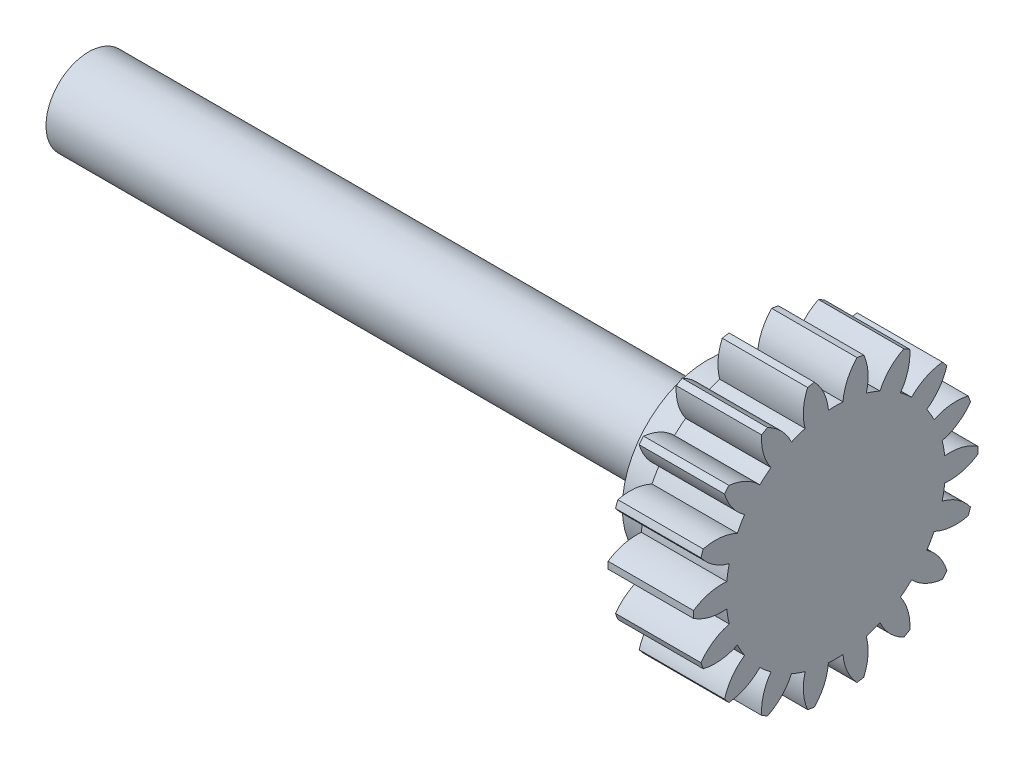
SolidWorks part; units mm, degrees
material "PET"
ref_plane "Plane1" through (0, 0, 0) normal (0, 0, 1) x (1, 0, 0)
ref_plane "Plane2" through (0, 0, 0) normal (0, 1, 0) x (1, 0, 0)
ref_plane "Plane3" through (0, 0, 0) normal (1, 0, 0) x (0, 0, -1)
sketch "HoldingSke" plane through (0, 0, 0) normal (0, 1, 0) x (1, 0, 0)
  line L0 (0, 0) -> (1159.5281, -376.7535)
  line L1 (-15, 0) -> (100, 0) construction
  line L2 (0, 0) -> (-2.1039, 2.3779)
  line L3 (0, 0) -> (-11.863, 4.5341)
  line L4 (0, 0) -> (8.2133, 2.6687)
  line L5 (0, 0) -> (-47.5972, -17.7524)
  line L6 (0, 0) -> (-2.632, -1.7758)
  line L7 (-2.1039, 2.3779) -> (8.8308, 51.9873)
  line L8 (-76.2, 54.61) -> (-75.184, 54.61)
  line L9 (-71.009, 38.7566) -> (-53.1078, 45.2721)
  line L10 (-76.2, 71.12) -> (104.1128, 71.12)
  line L11 (0, 0) -> (-3.175, 0)
  line L12 (-76.2, 101.6) -> (-76.1787, 101.6)
  line L13 (24.9733, 27.94) -> (52.9518, 28.4284)
  line L14 (24.9733, 27.94) -> (25.0241, 27.9398)
  line L15 (24.9733, 27.94) -> (100.4021, 29.52)
  circle A0 centre (0, 0) radius 0.3969
  circle A1 centre (0, 0) radius 4.0767
  circle A2 centre (0, 0) radius 38.1
  circle A3 centre (0, 0) radius 0.3969
  dimension "MHD" = 8.1534
  dimension "Hub_dia" = 76.2
  dimension "Bore" = 0.7937
  dimension "MBD" = 0.7937
  dimension "Num_teeth" = 18
  dimension "Pitch" = 1219.2
  dimension "Overall_len" = 50.8
  dimension "Show_teeth" = 18
  dimension "Thickness" = 3.175
  dimension "OAL" = 50.8002
  dimension "T_dim" = 1.016
  dimension "Ap" = 20
  dimension "H" = 19.05
  dimension "Pitch_radius" = 180.3128
  dimension "Width" = 3.175
  dimension "Backlash" = 0.0213
  dimension "Addendum_fac" = 1
  dimension "Dedendum_fac" = 1.2
  dimension "Clearance_fac" = 0.2
  dimension "Dedendum_add" = 0.0508
sketch "BasProSke" plane through (0, 0, 0) normal (0, 1, 0) x (1, 0, 0)
  line L0 (-10, 0) -> (60, 0) construction
  line L1 (0, 0) -> (0, 5.2917)
  line L2 (0, 0) -> (3.175, 0)
  line L3 (3.175, 0) -> (3.175, 5.2917)
  line L4 (3.175, 5.2917) -> (0, 5.2917)
  dimension "Thickness" = 3.175
  dimension "Diameter" = 10.5833
revolve "Base-Revolve" add sketch "BasProSke" angle 360 about L0
sketch "TooCutSke" plane through (0, 0, 0) normal (1, 0, 0) x (0, 0, -1)
  line L1 (0, 0) -> (0, 107) construction
  line L2 (0, 0) -> (-0.4524, 4.741) construction
  line L3 (0, 0) -> (-1.6488, 9.3507) construction
  line L4 (-0.4524, 4.741) -> (-0.8244, 4.6754) construction
  arc A0 (0.27, 4.0677) -> (-0.27, 4.0677) centre (0, 0) ccw
  arc A1 (0.8145, 5.2543) -> (-0.8145, 5.2543) centre (0, 0) ccw
  circle A2 centre (0, 0) radius 4.7625 construction
  circle A3 centre (0, 0) radius 4.4753 construction
  arc A4 (-0.27, 4.0677) -> (-0.8145, 5.2543) centre (-2.1688, 3.9146) ccw
  arc A5 (0.8145, 5.2543) -> (0.27, 4.0677) centre (2.1688, 3.9146) ccw
  dimension "Root_dia" = 8.1534
  dimension "Overcut_dia" = 10.6341
  dimension "Pitch_dia" = 9.525
  dimension "Base_dia" = 8.9506
  dimension "Flank_rad" = 1.905
  dimension "Half_ang" = 10
  dimension "Half_CT" = 0.3777
extrude "ToothCut" cut sketch "TooCutSke" along normal through all
fillet "Breaks" [suppressed] radius 0.0106 tangent propagation no
fillet "RootFillets" [suppressed] radius 0.1566
pattern_circular "TeethCuts" count 18 every 20 about axis through (-10, 0, 0) along (1, 0, 0) of "ToothCut", "RootFillets", "Breaks"
sketch "HubNeaOneSke" plane through (0, 0, 0) normal (-1, 0, 0) x (0, 0, 1)
  circle A0 centre (0, 0) radius 4.0767
  dimension "Diameter" = 8.1534
extrude "HubNearOne" [suppressed] add sketch "HubNeaOneSke" along normal blind 47.6252
sketch "HubNeaBotSke" plane through (0, 0, 0) normal (-1, 0, 0) x (0, 0, 1)
  circle A0 centre (0, 0) radius 4.0767
  dimension "Diameter" = 8.1534
extrude "HubNearBoth" [suppressed] add sketch "HubNeaBotSke" along normal blind 23.8126
ref_plane "FarPln" through (3.175, 0, 0) normal (1, 0, 0) x (0, 0, -1)
sketch "HubFarSke" plane through (3.175, 0, 0) normal (1, 0, 0) x (0, 0, -1)
  circle A0 centre (0, 0) radius 4.0767
  dimension "Diameter" = 8.1534
extrude "HubFar" [suppressed] add sketch "HubFarSke" along normal blind 23.8126
sketch "BorSke" plane through (0, 0, 0) normal (1, 0, 0) x (0, 0, -1)
  circle A0 centre (0, 0) radius 0.3969
  dimension "Diameter" = 0.7937
extrude "Bore" [suppressed] cut sketch "BorSke" along normal mid plane 101.6004
sketch "KeySke" plane through (0, 0, 0) normal (1, 0, 0) x (0, 0, -1)
  line L0 (-0.127, 0) -> (-0.127, 0.6191)
  line L1 (-0.127, 0.6191) -> (0.127, 0.6191)
  line L2 (0.127, 0.6191) -> (0.127, 0)
  line L3 (0, 0) -> (0, 34) construction
  line L4 (-0.127, 0) -> (0.127, 0)
  dimension "Offset" = 0.6191
  dimension "Width" = 0.254
extrude "Keyway" [suppressed] cut sketch "KeySke" along normal mid plane 101.6004
pattern_circular "Keyway2" [suppressed] count 2 every 90 about axis through (-10, 0, 0) along (1, 0, 0) reverse direction yes
sketch "Sketch1" [suppressed] plane through (0, 0, 0) normal (-1, 0, 0) x (0, 0, 1)
  circle A0 centre (0, 0) radius 2.7781
  dimension "D1" = 5.5562
extrude "Cut-Extrude2" [suppressed] cut sketch "Sketch1" against normal offset from surface (1.5875 mm away) 1.5875
sketch "Sketch2" plane through (0, 0, 0) normal (-1, 0, 0) x (0, 0, 1)
  circle A0 centre (0, 0) radius 1.5875
  dimension "D1" = 3.175
extrude "Cut-Extrude3" [suppressed] cut sketch "Sketch2" against normal through all contours A0
extrude "Boss-Extrude1" add sketch "Sketch2<3>" along normal blind 24.6062
sketch "Sketch2<3>" plane through (0, 0, 0) normal (-1, 0, 0) x (0, 0, 1) same geometry as "Sketch2"
sketch "Sketch3" plane through (0, 0, 0) normal (-1, 0, 0) x (0, 0, 1)
  circle A0 centre (0, 0) radius 3.175
  dimension "D1" = 6.35
extrude "Boss-Extrude2" add sketch "Sketch3" along normal blind 1.5875
ref_plane "Plane4" through (1.5875, 0, 0) normal (1, 0, 0) x (0, 0, -1)
sketch "Sketch4" plane through (1.5875, 0, 0) normal (1, 0, 0) x (0, 0, -1)
  circle A0 centre (0, 0) radius 4.7625
  dimension "D1" = 9.525
equation "' \"Pitch@HoldingSke\" = 4"
equation "'\"Num_teeth@HoldingSke\" = 18"
equation "' \"Ap@HoldingSke\" =  20"
equation "' \"Ap@HoldingSke\" = 20"
equation "' \"Width@HoldingSke\" = 0.5"
equation "' \"Hub_dia@HoldingSke\"= 1"
equation "' \"Hub_dia@HoldingSke\" = 1"
equation "' \"Overall_len@HoldingSke\" = 1.0"
equation "' \"Bore@HoldingSke\" = 0.75"
equation "' \"T_dim@HoldingSke\" = 0.85"
equation "' \"Width@KeySke\" = 0.25"
equation "' \"Show_teeth@HoldingSke\" = 13"
equation "' \"Backlash@HoldingSke\" = 0.009"
equation "' \"Addendum_fac@HoldingSke\" = 1.0"
equation "' \"Dedendum_fac@HoldingSke\" = 1.25"
equation "' \"Dedendum_add@HoldingSke\" = 0.00005"
equation "' \"Clearance_fac@HoldingSke\" = 0.25"
equation "' \"Pitch@HoldingSke\" = 0.5"
equation "' \"Num_teeth@HoldingSke\" = 23"
equation "' \"Show_teeth@HoldingSke\" = 23"
equation "' \"Backlash@HoldingSke\" = 0.0375"
equation "\"Overcut_dia@TooCutSke\" = (\"Num_teeth@HoldingSke\" + 2 * \"Addendum_fac@HoldingSke\") / \"Pitch@HoldingSke\" + 0.002"
equation "\"Pitch_dia@TooCutSke\" = \"Num_teeth@HoldingSke\" / \"Pitch@HoldingSke\""
equation "\"Base_dia@TooCutSke\" = \"Num_teeth@HoldingSke\" / \"Pitch@HoldingSke\" * cos((\"Ap@HoldingSke\"  * 3.14159265 / 180))"
equation "\"Root_dia@TooCutSke\" = (\"Num_teeth@HoldingSke\" + 2) / \"Pitch@HoldingSke\" - 2 * (\"Addendum_fac@HoldingSke\" + \"Dedendum_fac@HoldingSke\") / \"Pitch@HoldingSke\" - \"Dedendum_add@HoldingSke\" * 2"
equation "\"Half_ang@TooCutSke\" = 180 / \"Num_teeth@HoldingSke\""
equation "\"Half_CT@TooCutSke\" = \"Num_teeth@HoldingSke\" / \"Pitch@HoldingSke\" * sin((3.14159265 / 2 / \"Num_teeth@HoldingSke\")) / 2 - 7 * \"Backlash@HoldingSke\" / 4"
equation "\"Flank_rad@TooCutSke\" = \"Num_teeth@HoldingSke\" / \"Pitch@HoldingSke\" / 5"
equation "\"Radius@RootFillets\" = \"Clearance_fac@HoldingSke\" / \"Pitch@HoldingSke\" + \"Dedendum_add@HoldingSke\""
equation "\"Break_rad@Breaks\" = 0.02 / \"Pitch@HoldingSke\""
equation "\"Thickness@HoldingSke\" = \"Width@HoldingSke\""
equation "\"OAL@HoldingSke\" = \"Thickness@HoldingSke\""
equation "\"MHD@HoldingSke\" = (\"Num_teeth@HoldingSke\" + 2) / \"Pitch@HoldingSke\" - 2 * (\"Addendum_fac@HoldingSke\" + \"Dedendum_fac@HoldingSke\")  / \"Pitch@HoldingSke\" - \"Dedendum_add@HoldingSke\" * 2"
equation "\"MBD@HoldingSke\" = (\"Num_teeth@HoldingSke\" + 2) / \"Pitch@HoldingSke\" - 2 * (\"Addendum_fac@HoldingSke\" + \"Dedendum_fac@HoldingSke\")  / \"Pitch@HoldingSke\" - \"Dedendum_add@HoldingSke\" * 2 - 0.002"
equation "\"MHD@HoldingSke\" = ((sgn( \"MHD@HoldingSke\" - \"Hub_dia@HoldingSke\" )-1)*( \"MHD@HoldingSke\" - \"Hub_dia@HoldingSke\" ))/-2+ \"Hub_dia@HoldingSke\""
equation "\"MBD@HoldingSke\" = ((sgn( \"MBD@HoldingSke\" - \"Bore@HoldingSke\" )-1)*( \"MBD@HoldingSke\" - \"Bore@HoldingSke\" ))/-2+ \"Bore@HoldingSke\""
equation "\"OAL@HoldingSke\" = ((sgn( \"OAL@HoldingSke\" - \"Overall_len@HoldingSke\" )+1)*( \"OAL@HoldingSke\" - \"Overall_len@HoldingSke\" ))/2 + \"Overall_len@HoldingSke\" + 0.000002"
equation "\"Num_teeth@TeethCuts\" = int( \"Show_teeth@HoldingSke\" ) + 1"
equation "\"Num_teeth@TeethCuts\" = ((sgn( \"Num_teeth@TeethCuts\" - \"Num_teeth@HoldingSke\" )-1)*( \"Num_teeth@TeethCuts\" - \"Num_teeth@HoldingSke\" ))/-2+ \"Num_teeth@HoldingSke\""
equation "\"Num_teeth@TeethCuts\" = ((sgn( \"Num_teeth@TeethCuts\" - 2.0)+1)*( \"Num_teeth@TeethCuts\" - 2.0))/2 +2.0"
equation "\"Angle@TeethCuts\" = 360.0 / \"Num_teeth@HoldingSke\""
equation "\"Diameter@BasProSke\" = (\"Num_teeth@HoldingSke\" + 2 * \"Addendum_fac@HoldingSke\") / \"Pitch@HoldingSke\""
equation "\"Thickness@BasProSke\"  = \"Thickness@HoldingSke\""
equation "' \"Fillet_rad@BasProSke\" =  \"Thickness@HoldingSke\" * 0.05"
equation "' \"Fillet_rad@BasProSke\" = \"Thickness@HoldingSke\" * 0.05"
equation "\"MHD@HoldingSke\" = ((sgn( \"MHD@HoldingSke\" - \"Root_dia@TooCutSke\" )-1)*( \"MHD@HoldingSke\" - \"Root_dia@TooCutSke\" ))/-2+ \"Root_dia@TooCutSke\""
equation "\"Diameter@HubNeaOneSke\" = \"MHD@HoldingSke\""
equation "\"Length@HubNearOne\" = \"OAL@HoldingSke\" - \"Thickness@BasProSke\""
equation "\"Diameter@HubNeaBotSke\" = \"MHD@HoldingSke\""
equation "\"Length@HubNearBoth\" = ( \"OAL@HoldingSke\" - \"Thickness@BasProSke\" ) / 2.0"
equation "\"Thickness@FarPln\" = \"Thickness@BasProSke\""
equation "\"Diameter@HubFarSke\" = \"MHD@HoldingSke\""
equation "\"Length@HubFar\" = ( \"OAL@HoldingSke\" - \"Thickness@BasProSke\" ) / 2.0"
equation "\"Diameter@BorSke\" = \"MBD@HoldingSke\""
equation "\"D1@Bore\" = \"OAL@HoldingSke\" * 2.0"
equation "\"D1@Keyway\" = \"OAL@HoldingSke\" * 2.0"
equation "\"Offset@KeySke\" = \"T_dim@HoldingSke\" - \"MBD@HoldingSke\" / 2.0"
